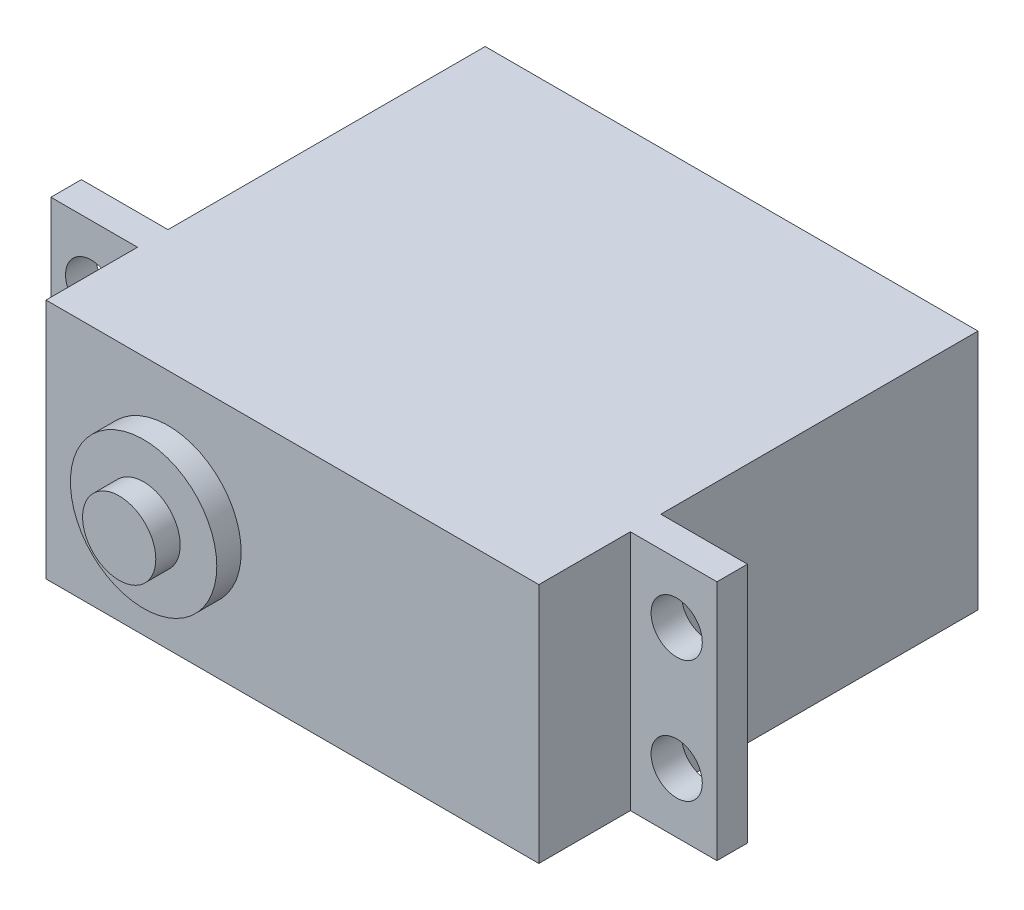
SolidWorks part; units mm, degrees
ref_plane "Front Plane" through (0, 0, 0) normal (0, 0, 1) x (1, 0, 0)
ref_plane "Top Plane" through (0, 0, 0) normal (0, 1, 0) x (1, 0, 0)
ref_plane "Right Plane" through (0, 0, 0) normal (1, 0, 0) x (0, 0, -1)
sketch "Sketch1" plane through (0, 0, 0) normal (0, 0, 1) x (1, 0, 0)
  line L0 (-10, -9.9) -> (30.4, -9.9)
  line L1 (30.4, -9.9) -> (30.4, 9.9)
  line L2 (30.4, 9.9) -> (-10, 9.9)
  line L3 (-10, 9.9) -> (-10, -9.9)
extrude "Boss-Extrude1" add sketch "Sketch1" along normal blind 10 and the other way blind 26
sketch "Sketch2" plane through (0, 0, 0) normal (0, 0, 1) x (1, 0, 0)
  line L0 (-17.1, -9.9) -> (-10, -9.9)
  line L1 (-10, -9.9) -> (-10, 9.9)
  line L2 (-10, 9.9) -> (-17.1, 9.9)
  line L3 (-17.1, 9.9) -> (-17.1, -9.9)
  circle A0 centre (-13.8, 5) radius 2.1
  circle A1 centre (-13.8, -5) radius 2.1
extrude "Boss-Extrude2" add sketch "Sketch2" along normal blind 2.5
sketch "Sketch3" plane through (0, 0, 0) normal (0, 0, 1) x (1, 0, 0)
  line L0 (30.4, -9.9) -> (37.5, -9.9)
  line L1 (37.5, -9.9) -> (37.5, 9.9)
  line L2 (37.5, 9.9) -> (30.4, 9.9)
  line L3 (30.4, 9.9) -> (30.4, -9.9)
  circle A0 centre (34.2, 5) radius 2.1
  circle A1 centre (34.2, -5) radius 2.1
extrude "Boss-Extrude3" add sketch "Sketch3" along normal blind 2.5
sketch "Sketch4" plane through (0, 0, 0) normal (0, 0, 1) x (1, 0, 0)
  circle A0 centre (0, 0) radius 6
extrude "Boss-Extrude4" add sketch "Sketch4" along normal blind 2 from offset 10
sketch "Sketch5" plane through (0, 0, 0) normal (0, 0, 1) x (1, 0, 0)
  circle A0 centre (0, 0) radius 3
extrude "Boss-Extrude5" add sketch "Sketch5" along normal blind 2 from offset 12
ref_axis "Shaft" through (0, 0, 16) along (0, 0, -1)
ref_plane "SplineTop" through (0, 0, 14) normal (0, 0, 1) x (1, 0, 0)
